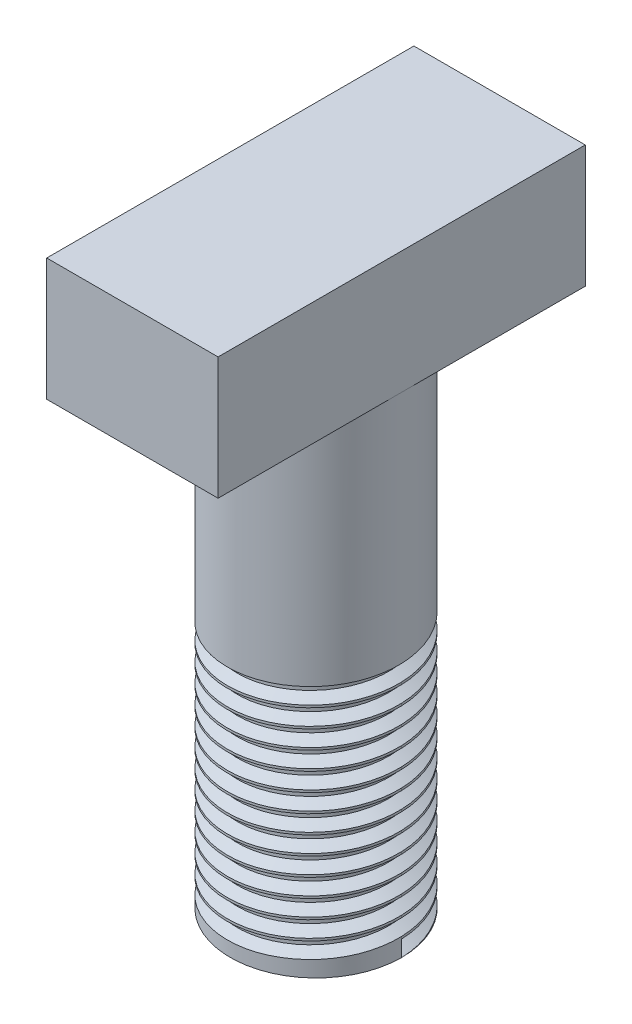
SolidWorks part; units mm, degrees
ref_plane "Front Plane" through (0, 0, 0) normal (0, 0, 1) x (1, 0, 0)
ref_plane "Top Plane" through (0, 0, 0) normal (0, 1, 0) x (1, 0, 0)
ref_plane "Right Plane" through (0, 0, 0) normal (1, 0, 0) x (0, 0, -1)
sketch "Sketch1" plane through (0, 0, 0) normal (0, 1, 0) x (1, 0, 0)
  circle A0 centre (0, 0) radius 7
  dimension "D1" = 14
extrude "Boss-Extrude1" add sketch "Sketch1" against normal blind 40
thread "Thread1" pitch 1.5 method cut profile "Thread Profile2" start angle 0, offset 0, length 20, pitch 1.5, diameter 14
ref_plane "Plane2" through (7, -40, 0) normal (0, 0, 1) x (1, 0, 0)
sketch "Thread Profile2" plane through (7, -40, 0) normal (0, 0, 1) x (1, 0, 0)
  line L0 (0, 0) -> (0, 1.5) construction
  line L11 (0, 0) -> (0, 1.3125)
  line L12 (0, 1.3125) -> (-0.8119, 0.8437)
  line L13 (-0.8119, 0.8437) -> (-0.8119, 0.4687)
  line L15 (-0.8119, 0.4687) -> (0, 0)
  line L17 (-0.8119, 0.6562) -> (0, 0.6562) construction
  point P2 (0, 0)
  dimension "Pitch" = 1.5
  dimension "Profile_Angle" = 60
  dimension "Profile_Land" = 0.375
  dimension "Profile_Height" = 0.8119
sketch "Sketch12" plane through (0, 0, 0) normal (0, 1, 0) x (1, 0, 0)
  line L1 (7, -15) -> (-7, -15)
  line L2 (7, -15) -> (7, 15)
  line L3 (7, 15) -> (-7, 15)
  line L4 (-7, -15) -> (-7, 15)
  line L5 (7, -15) -> (-7, 15) construction
  line L6 (7, 15) -> (-7, -15) construction
  point P0 (0, 0)
  dimension "D1" = 30
  dimension "D2" = 14
extrude "Boss-Extrude2" add sketch "Sketch12" along normal blind 10
